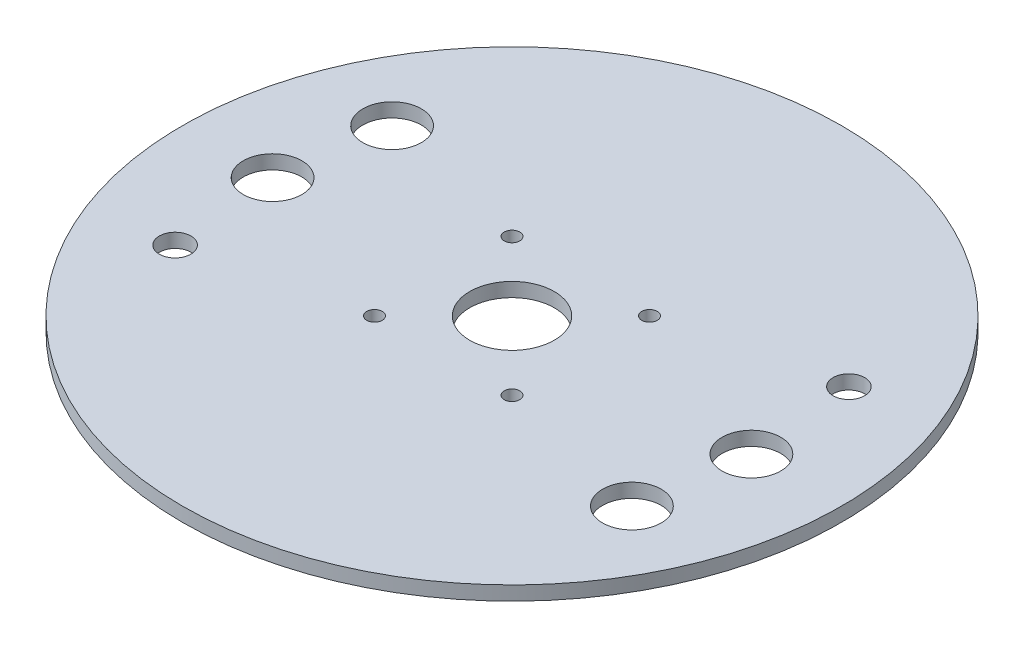
SolidWorks part; units mm, degrees
ref_plane "Front Plane" through (0, 0, 0) normal (0, 0, 1) x (1, 0, 0)
ref_plane "Top Plane" through (0, 0, 0) normal (0, 1, 0) x (1, 0, 0)
ref_plane "Right Plane" through (0, 0, 0) normal (1, 0, 0) x (0, 0, -1)
sketch "Sketch1" plane through (0, 0, 0) normal (0, 1, 0) x (1, 0, 0)
  circle A0 centre (0, 0) radius 74.295
  circle A1 centre (0, 0) radius 9.525
extrude "Boss-Extrude1" add sketch "Sketch1" along normal blind 3.175
sketch "Sketch2" plane through (0, 3.175, 0) normal (0, 1, 0) x (1, 0, 0)
  line L0 (53.975, 0) -> (-53.975, 0) construction
  line L1 (51.7955, 24.1526) -> (-51.7955, -24.1526) construction
  line L2 (0, 0) -> (50.6445, -23.6159) construction
  line L3 (0, 0) -> (-50.6445, 23.6159) construction
  circle A0 centre (-53.975, 0) radius 6.604
  circle A1 centre (53.975, 0) radius 6.604
  circle A2 centre (-51.7955, -24.1526) radius 3.556
  circle A3 centre (51.7955, 24.1526) radius 3.556
  circle A4 centre (50.6445, -23.6159) radius 6.604
  circle A5 centre (-50.6445, 23.6159) radius 6.604
  point P5 (0, 0)
  point P9 (0, 0)
extrude "Cut-Extrude1" cut sketch "Sketch2" against normal blind 3.175
sketch "Sketch3" plane through (0, 3.175, 0) normal (0, 1, 0) x (1, 0, 0)
  line L0 (0, -15.5) -> (0, 15.5) construction
  line L1 (15.5, 15.5) -> (-15.5, 15.5) construction
  line L2 (15.5, -15.5) -> (-15.5, -15.5) construction
  circle A0 centre (15.5, 15.5) radius 1.75
  circle A1 centre (15.5, -15.5) radius 1.75
  circle A2 centre (-15.5, -15.5) radius 1.75
  circle A3 centre (-15.5, 15.5) radius 1.75
  point P4 (0, 0)
  point P8 (0, 15.5)
  point P11 (0, -15.5)
extrude "Cut-Extrude2" cut sketch "Sketch3" against normal blind 50.8
